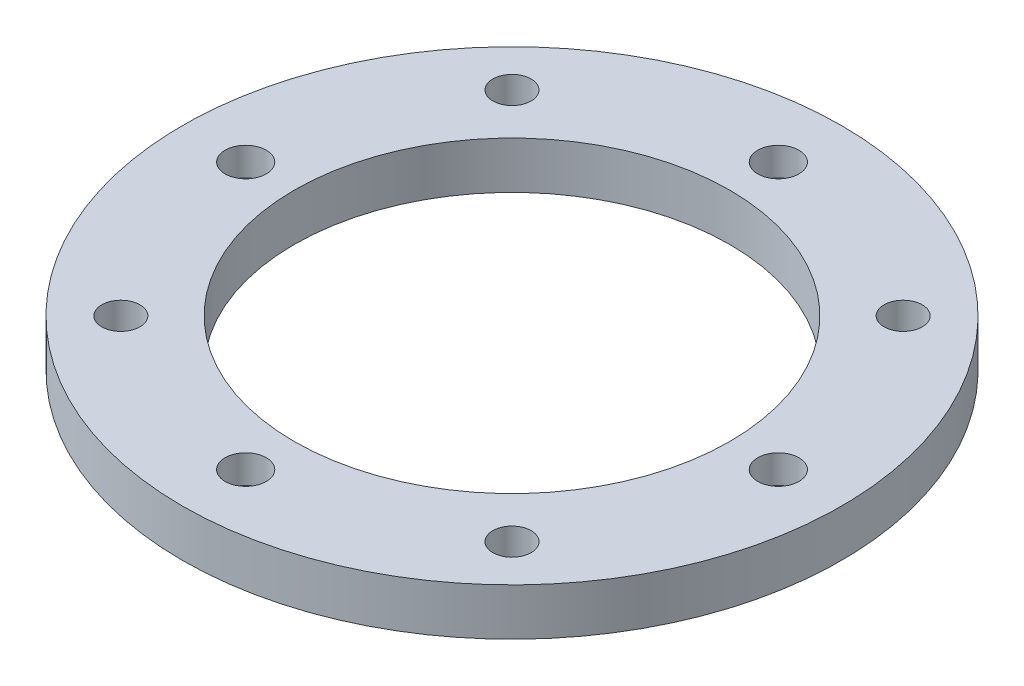
SolidWorks part; units mm, degrees
material "6061 Alloy"
ref_plane "Front Plane" through (0, 0, 0) normal (0, 0, 1) x (1, 0, 0)
ref_plane "Top Plane" through (0, 0, 0) normal (0, 1, 0) x (1, 0, 0)
ref_plane "Right Plane" through (0, 0, 0) normal (1, 0, 0) x (0, 0, -1)
sketch "Sketch1" plane through (0, 0, 0) normal (0, 1, 0) x (1, 0, 0)
  line L1 (-88.9, -88.9) -> (88.9, -88.9)
  line L2 (-88.9, -88.9) -> (-88.9, 88.9)
  line L3 (-88.9, 88.9) -> (88.9, 88.9)
  line L4 (88.9, -88.9) -> (88.9, 88.9)
  line L5 (-88.9, -88.9) -> (88.9, 88.9) construction
  line L6 (-88.9, 88.9) -> (88.9, -88.9) construction
  point P0 (0, 0)
  dimension "D1" = 177.8
extrude "Boss-Extrude1" add sketch "Sketch1" along normal blind 12.7
sketch "Sketch2" plane through (0, 12.7, 0) normal (0, 1, 0) x (1, 0, 0)
  line L1 (-52.759, -52.759) -> (52.759, -52.759) construction
  line L2 (-52.759, -52.759) -> (-52.759, 52.759) construction
  line L3 (-52.759, 52.759) -> (52.759, 52.759) construction
  line L4 (52.759, -52.759) -> (52.759, 52.759) construction
  line L5 (-52.759, -52.759) -> (52.759, 52.759) construction
  line L6 (-52.759, 52.759) -> (52.759, -52.759) construction
  circle A0 centre (0, 0) radius 74.6125 construction
  point P3 (-52.759, 52.759)
  point P4 (52.759, 52.759)
  point P5 (52.759, -52.759)
  point P6 (-52.759, -52.759)
  dimension "D1" = 149.225
hole_wizard "13/32 (0.40625) Diameter Hole1" positions "3DSketch1" profile "Sketch3" hole size "13/32" standard "ANSI Inch" end condition through all
sketch3d "3DSketch1"
  point P0 (-52.759, 12.7, -52.759)
  point P3 (52.759, 12.7, -52.759)
  point P6 (52.759, 12.7, 52.759)
  point P9 (-52.759, 12.7, 52.759)
sketch "Sketch3" plane through (-52.759, 12.7, -52.759) normal (1, 0, 0) x (0, 0, 1)
  line L0 (0, 0) -> (0, 12.7)
  line L1 (0, 12.7) -> (5.1594, 12.7)
  line L2 (5.1594, 12.7) -> (5.1594, 0)
  line L5 (5.1594, 0) -> (0, 0)
  line L11 (0, -6.35) -> (0, 107.95) construction
  dimension "Thru Hole Dia." = 10.3187
  dimension "Thru Hole Depth" = 12.7
sketch "Sketch4" plane through (0, 12.7, 0) normal (0, 1, 0) x (1, 0, 0)
  circle A0 centre (0, 0) radius 58.7375
  dimension "D1" = 117.475
extrude "Cut-Extrude1" cut sketch "Sketch4" against normal through all
sketch "Sketch5" plane through (0, 12.7, 0) normal (0, 1, 0) x (1, 0, 0)
  line L0 (88.9, 88.9) -> (-88.9, 88.9) construction
  circle A0 centre (0, 0) radius 88.9
extrude "Cut-Extrude2" cut sketch "Sketch5" against normal blind 12.7 flip side to cut
sketch "Sketch6" plane through (0, 12.7, 0) normal (0, 1, 0) x (1, 0, 0)
  line L0 (-71.842, 0) -> (0, 0) construction
  line L1 (0, 0) -> (71.842, 0) construction
  line L2 (71.842, 0) -> (0, 71.842) construction
  line L3 (0, 71.842) -> (0, 0) construction
  line L4 (0, 0) -> (0, -71.842) construction
  point P0 (0, 71.842)
  point P1 (71.842, 0)
  point P4 (-71.842, 0)
  point P5 (0, -71.842)
  dimension "D2" = 101.6
hole_wizard "CBORE for 1/4 Socket Head Cap Screw1" positions "3DSketch2" profile "Sketch9" counterbore size "1/4" standard "ANSI Inch" end condition through all
sketch3d "3DSketch2"
  point P0 (0, 12.7, -71.842)
  point P3 (71.842, 12.7, 0)
  point P6 (-71.842, 12.7, 0)
  point P9 (0, 12.7, 71.842)
sketch "Sketch9" plane through (0, 12.7, -71.842) normal (1, 0, 0) x (0, 0, 1)
  line L0 (0, 0) -> (0, 12.7)
  line L1 (0, 12.7) -> (3.3782, 12.7)
  line L3 (3.3782, 12.7) -> (3.3782, 7.62)
  line L4 (3.3782, 7.62) -> (5.5562, 7.62)
  line L5 (5.5562, 7.62) -> (5.5562, 0)
  line L7 (5.5562, 0) -> (0, 0)
  line L11 (0, -6.35) -> (0, 107.95) construction
  dimension "Thru Hole Dia." = 6.7564
  dimension "Thru Hole Depth" = 12.7
  dimension "C'Bore Dia." = 11.1125
  dimension "C'Bore Depth" = 7.62
